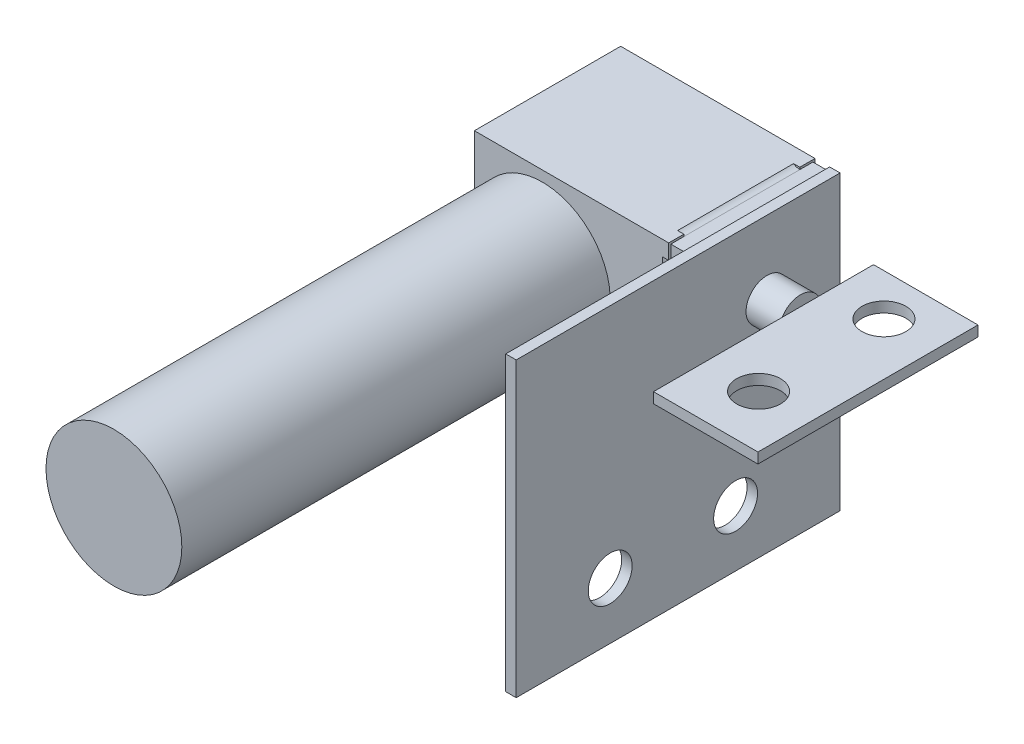
SolidWorks part; units mm, degrees
material "銅"
ref_plane "正面" through (0, 0, 0) normal (0, 0, 1) x (1, 0, 0)
ref_plane "平面" through (0, 0, 0) normal (0, 1, 0) x (1, 0, 0)
ref_plane "右側面" through (0, 0, 0) normal (1, 0, 0) x (0, 0, -1)
sketch "Sketch1" plane through (0, 0, 0) normal (0, 1, 0) x (1, 0, 0)
  line L1 (-4.5, 3.5) -> (4.5, 3.5)
  line L2 (-4.5, 3.5) -> (-4.5, -3.5)
  line L3 (-4.5, -3.5) -> (4.5, -3.5)
  line L4 (4.5, 3.5) -> (4.5, -3.5)
  line L5 (-4.5, 3.5) -> (4.5, -3.5) construction
  line L6 (-4.5, -3.5) -> (4.5, 3.5) construction
  point P0 (0, 0)
  dimension "D1" = 9
  dimension "D2" = 7
extrude "Boss-Extrude1" add sketch "Sketch1" along normal blind 7
sketch "Sketch4" plane through (4.5, 0, 0) normal (1, 0, 0) x (0, 0, -1)
  line L1 (-3.5, 7) -> (-2.775, 7)
  line L2 (-3.5, 7) -> (-3.5, 6.275)
  line L3 (-3.5, 6.275) -> (-2.775, 6.275)
  line L4 (-2.775, 7) -> (-2.775, 6.275)
  line L5 (3.5, 7) -> (2.775, 7)
  line L6 (3.5, 7) -> (3.5, 6.275)
  line L7 (3.5, 6.275) -> (2.775, 6.275)
  line L8 (2.775, 7) -> (2.775, 6.275)
  line L9 (-3.5, 0) -> (-2.775, 0)
  line L10 (-3.5, 0) -> (-3.5, 0.725)
  line L11 (-3.5, 0.725) -> (-2.775, 0.725)
  line L12 (-2.775, 0) -> (-2.775, 0.725)
  line L13 (3.5, 0) -> (2.775, 0)
  line L14 (3.5, 0) -> (3.5, 0.725)
  line L15 (3.5, 0.725) -> (2.775, 0.725)
  line L16 (2.775, 0) -> (2.775, 0.725)
  dimension "D1" = 0.725
  dimension "D2" = 0.725
  dimension "D3" = 0.725
  dimension "D4" = 0.725
  dimension "D5" = 0.725
  dimension "D6" = 0.725
  dimension "D7" = 0.725
  dimension "D8" = 0.725
extrude "Boss-Extrude3" add sketch "Sketch4" along normal blind 0.3
ref_plane "Plane1" through (4.5, 0, 0) normal (1, 0, 0) x (0, 0, -1)
sketch "Sketch7" plane through (4.5, 0, 0) normal (1, 0, 0) x (0, 0, -1)
  line L0 (-3.5, 6.275) -> (-3.5, 0.725) construction
  line L1 (-2.775, 0) -> (2.775, 0) construction
  line L2 (-3.4, 1.1) -> (3.4, 1.1)
  line L3 (-3.4, 1.1) -> (-3.4, 0.1)
  line L4 (-3.4, 0.1) -> (3.4, 0.1)
  line L6 (3.4, 1.1) -> (3.4, 0.1)
  line L7 (-3.4, 6.9) -> (3.4, 6.9)
  line L8 (-3.4, 6.9) -> (-3.4, 5.9)
  line L9 (-3.4, 5.9) -> (3.4, 5.9)
  line L10 (3.4, 6.9) -> (3.4, 5.9)
  line L11 (-3.5, 0.725) -> (-3.5, 0) construction
  line L12 (3.5, 0) -> (3.5, 0.725) construction
  line L13 (3.5, 6.275) -> (3.5, 7) construction
  line L15 (-2.775, 7) -> (2.775, 7) construction
  dimension "D1" = 0.1
  dimension "D2" = 0.1
  dimension "D3" = 0.1
  dimension "D4" = 1
  dimension "D5" = 1
  dimension "D6" = 0.1
  dimension "D7" = 0.1
  dimension "D8" = 0.1
extrude "Boss-Extrude5" add sketch "Sketch7" along normal blind 1
fillet "Fillet1" radius 0.5 8 edges at (4.5, 6.9, 0) (4.5, 6.0875, 3.4) (4.5, 5.9, 0) (4.5, 6.0875, -3.4) (4.5, 0.9125, -3.4) (4.5, 1.1, 0) (4.5, 0.9125, 3.4) (4.5, 0.1, 0)
sketch "Sketch8" plane through (5.5, 0, 0) normal (1, 0, 0) x (0, 0, -1)
  line L1 (-12, -7) -> (3.5, -7)
  line L2 (-12, -7) -> (-12, 7)
  line L3 (-12, 7) -> (3.5, 7)
  line L4 (3.5, -7) -> (3.5, 7)
  line L5 (3.5, 0) -> (-3.5, 0) construction
  line L6 (3.5, 6.275) -> (3.5, 7) construction
  dimension "D1" = 0
  dimension "D2" = 7
  dimension "D3" = 14
  dimension "D4" = 15.5
extrude "Boss-Extrude6" add sketch "Sketch8" along normal blind 0.5
sketch "ｽｹｯﾁ6" plane through (5.5, 0, 0) normal (-1, 0, 0) x (0, 0, 1)
  line L1 (-3.5, -7) -> (-3.5, 7) construction
  line L6 (-3.5, 7) -> (12, 7) construction
  circle A1 centre (0, 3.5) radius 1
  dimension "D1" = 3.5
  dimension "D3" = 3.5
extrude "ﾎﾞｽ - 押し出し9" add sketch "ｽｹｯﾁ6" against normal blind 2.1 and the other way up to vertex (1 mm away) other way up to point (4.5, 5.4, 3.5)
sketch "Sketch10" plane through (7.6, 0, 0) normal (1, 0, 0) x (0, 0, -1)
  line L0 (3.5, -7) -> (3.5, 7) construction
  line L1 (-7.03, 3.5) -> (-7.03, 4)
  line L2 (-7.03, 4) -> (3.5, 4)
  line L3 (3.5, 4) -> (3.5, 3.5)
  line L4 (-7.03, 3.5) -> (3.5, 3.5)
extrude "Boss-Extrude9" add sketch "Sketch10" along normal blind 5
sketch "ｽｹｯﾁ3" plane through (6, 0, 0) normal (1, 0, 0) x (0, 0, -1)
  line L0 (-12, -7) -> (3.5, -7) construction
  line L1 (3.5, -7) -> (3.5, 7) construction
  circle A0 centre (-1.5, -4.3) radius 1.05
  circle A1 centre (-7.5, -4.3) radius 1.05
  dimension "D1" = 2.7
  dimension "D2" = 2.7
  dimension "D3" = 11
  dimension "D4" = 5
extrude "ｶｯﾄ - 押し出し2" cut sketch "ｽｹｯﾁ3" along direction (-1, 0, 0) on the side against the normal up to vertex (0.5 mm away) up to point (5.5, 7, 12)
sketch "ｽｹｯﾁ5" plane through (0, 0, 3.5) normal (0, 0, 1) x (1, 0, 0)
  line L0 (-4.5, 7) -> (-4.5, 0) construction
  circle A0 centre (-1.25, 3.25) radius 3.25
  dimension "D1" = 3.25
extrude "ﾎﾞｽ - 押し出し2" add sketch "ｽｹｯﾁ5" along normal blind 20.5
sketch "ｽｹｯﾁ7" plane through (0, 3.5, 0) normal (0, -1, 0) x (-1, 0, 0)
  line L5 (-12.6, 3.5) -> (-7.6, 3.5) construction
  line L6 (-12.6, -7.03) -> (-12.6, 3.5) construction
  circle A4 centre (-10.1, -4.5) radius 1.05
  circle A5 centre (-10.1, 1.5) radius 1.05
  dimension "D1" = 2
  dimension "D2" = 8
  dimension "D3" = 2.5
  dimension "D4" = 2.5
extrude "ｶｯﾄ - 押し出し3" cut sketch "ｽｹｯﾁ7" against normal blind 1.6
